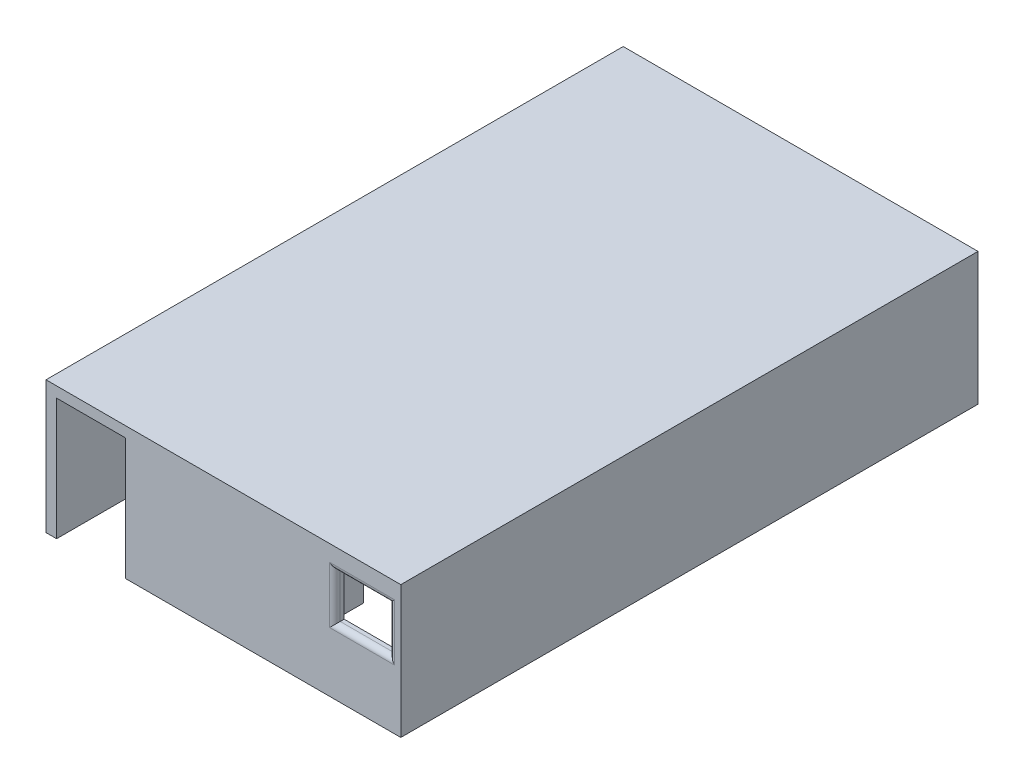
SolidWorks part; units mm, degrees
ref_plane "Front Plane" through (0, 0, 0) normal (0, 0, 1) x (1, 0, 0)
ref_plane "Top Plane" through (0, 0, 0) normal (0, 1, 0) x (1, 0, 0)
ref_plane "Right Plane" through (0, 0, 0) normal (1, 0, 0) x (0, 0, -1)
sketch "Sketch2" plane through (0, 0, 0) normal (0, 1, 0) x (1, 0, 0)
  line L0 (0, 10) -> (0, 20)
  line L1 (0, 20) -> (8, 20)
  line L2 (8, 20) -> (8, 14.2452)
  line L3 (0, 0) -> (22.3158, 22.3158) construction
  line L4 (10, 0) -> (22.3158, 0) construction
  line L5 (18, 8) -> (22.3158, 8) construction
  line L6 (2.9289, 2.9289) -> (9.4645, 9.4645)
  line L7 (9.4645, 9.4645) -> (13, 13)
  arc A0 (2.9289, 2.9289) -> (0, 10) centre (10, 10) cw
  arc A2 (13, 13) -> (8, 14.2452) centre (9.4645, 9.4645) ccw
  point P13 (8, 8)
  dimension "D2" = 10
  dimension "D5" = 10
  dimension "D1" = 8
  dimension "D4" = 20
other "AlignGroup1"
extrude "Boss-Extrude1" add sketch "Sketch2" along normal blind 29
ref_plane "Plane4" through (0, 24, 0) normal (0, 1, 0) x (1, 0, 0)
sketch "Sketch8" [suppressed] plane through (0, 24, 0) normal (0, 1, 0) x (1, 0, 0)
  line L0 (2.9289, 2.9289) -> (13, 13) construction
ref_plane "Plane1" through (0, 0, 0) normal (0.7071, 0, 0.7071) x (0.7071, 0, -0.7071)
mirror "Mirror1" about plane through (0, 0, 0) normal (0.7071, 0, 0.7071) of "Boss-Extrude1"
sketch "Sketch3" plane through (0, 0, -20) normal (0, 0, -1) x (-1, 0, 0)
  line L0 (-4, 0) -> (-4, 4) construction
  line L2 (-8, 0) -> (0, 0) construction
  line L3 (-6.25, 4) -> (-6.25, 25)
  line L4 (-6.25, 4) -> (-1.75, 4)
  line L5 (-6.25, 14.5) -> (-1.75, 14.5) construction
  line L6 (-6.25, 25) -> (-1.75, 25)
  line L7 (-1.75, 4) -> (-1.75, 25)
  dimension "D1" = 4
  dimension "D2" = 4.5
extrude "Cut-Extrude1" cut sketch "Sketch3" against normal blind 6
mirror "Mirror2" about plane through (0, 0, 0) normal (0.7071, 0, 0.7071) of "Cut-Extrude1"
sketch "Sketch6" plane through (0, 29, 0) normal (0, 1, 0) x (1, 0, 0)
  circle A0 centre (10, 10) radius 2.15
extrude "Cut-Extrude2" cut sketch "Sketch6" against normal through all
ref_plane "Plane2" through (0, 14.5, 0) normal (0, 1, 0) x (1, 0, 0)
sketch "Sketch9" plane through (0, 24, 0) normal (0, 1, 0) x (1, 0, 0)
  line L0 (8.9391, 13.9595) -> (13.429, 18.4495)
  line L1 (7.1014, 7.1014) -> (11.0609, 6.0405)
  line L2 (11.0609, 6.0405) -> (13.9595, 8.9391)
  line L3 (13.9595, 8.9391) -> (18.4293, 13.7623)
  line L5 (8.9391, 13.9595) -> (6.0405, 11.0609)
  line L6 (6.0405, 11.0609) -> (7.1014, 7.1014)
  line L9 (13.429, 18.4495) -> (18.4293, 13.7623)
  line L11 (10.9188, 13.429) -> (8.9391, 13.9595) [skipped]
  line L12 (13.9595, 8.9391) -> (13.9481, 8.9817) [skipped]
  circle A0 centre (10, 10) radius 3.55 construction
  dimension "D1" = 7.1
extrude "Cut-Extrude3" cut sketch "Sketch9" against normal blind 3.5 contours L9 L3 L2 L1 L6 L5 L0
mirror "Mirror4" about plane through (0, 14.5, 0) normal (0, 1, 0) of "Cut-Extrude3"
sketch "Эскиз1" plane through (0, 0, -1.75) normal (0, 0, -1) x (-1, 0, 0)
  line L0 (-20, 4) -> (-20, 25) construction
  line L1 (-20, 0) -> (-39.5, 0)
  line L2 (-20, 0) -> (-20, 14.5)
  line L3 (-20, 14.5) -> (-39.5, 14.5)
  line L4 (-39.5, 0) -> (-39.5, 14.5)
  line L5 (-20, 0) -> (-10, 0) construction
  dimension "D1" = 14.5
  dimension "D2" = 19.5
extrude "Бобышка-Вытянуть1" add sketch "Эскиз1" along normal up to surface and the other way up to surface separate body up to face at (17.1226, 14.5, -8) other way up to face at (15, 14.5, 0)
sketch "Эскиз2" plane through (39.5, 0, 0) normal (1, 0, 0) x (0, 0, -1)
  line L1 (1.75, 14.5) -> (6.25, 14.5)
  line L2 (1.75, 14.5) -> (1.75, 13.5)
  line L3 (1.75, 13.5) -> (6.25, 13.5)
  line L4 (6.25, 14.5) -> (6.25, 13.5)
  line L6 (1.75, 4) -> (1.75, 25) construction
  line L7 (6.25, 25) -> (6.25, 4) construction
  dimension "D1" = 1
  dimension "D2" = 4.5
extrude "Вырез-Вытянуть1" cut sketch "Эскиз2" against normal up to surface (19.5 mm away) up to face at (20, 7.25, -4)
sketch "Эскиз4" plane through (0, 0, -8) normal (0, 0, -1) x (-1, 0, 0)
  line L0 (-20, 0) -> (-20, 14.5) construction
  line L1 (-24.5, 7.9124) -> (-20.5, 7.9124)
  line L2 (-24.5, 7.9124) -> (-24.5, 3.9124)
  line L3 (-24.5, 3.9124) -> (-20.5, 3.9124)
  line L4 (-20.5, 7.9124) -> (-20.5, 3.9124)
  line L6 (-20, 14.5) -> (-20, 0) construction
  dimension "D1" = 4
  dimension "D2" = 4
  dimension "D3" = 0.5
extrude "Вырез-Вытянуть3" cut sketch "Эскиз4" against normal blind 0.7
sketch "Эскиз5" plane through (0, 0, -8) normal (0, 0, -1) x (-1, 0, 0)
  line L1 (-26.5, 12) -> (-24.5, 12)
  line L2 (-26.5, 12) -> (-26.5, 0)
  line L3 (-26.5, 0) -> (-24.5, 0)
  line L4 (-24.5, 12) -> (-24.5, 0)
  line L5 (-24.5, 7.9124) -> (-24.5, 3.9124) construction
  line L6 (-39.5, 0) -> (-20, 0) construction
  dimension "D1" = 12
  dimension "D2" = 2
extrude "Вырез-Вытянуть4" cut sketch "Эскиз5" against normal up to surface (6.25 mm away) up to face at (29.75, 14, -1.75)
sketch "Эскиз6" plane through (0, 0, -8) normal (0, 0, -1) x (-1, 0, 0)
  line L1 (-37.5, 11) -> (-26.5, 11)
  line L2 (-37.5, 11) -> (-37.5, 0)
  line L3 (-37.5, 0) -> (-26.5, 0)
  line L4 (-26.5, 11) -> (-26.5, 0)
  line L5 (-24.5, 12) -> (-26.5, 12) construction
  line L6 (-26.5, 12) -> (-26.5, 0) construction
  dimension "D1" = 11
  dimension "D2" = 11
  dimension "D3" = 1
extrude "Вырез-Вытянуть5" cut sketch "Эскиз6" against normal up to surface (6.25 mm away) up to face at (29.75, 14, -1.75)
sketch "Эскиз7" plane through (0, 0, -1.75) normal (0, 0, -1) x (-1, 0, 0)
  line L0 (-27.0515, 6.093) -> (-37.3, 6.093) construction
  line L1 (-37.3, 10.4361) -> (-27.0515, 10.4361)
  line L2 (-37.3, 10.4361) -> (-37.3, 1.75)
  line L3 (-37.3, 1.75) -> (-27.0515, 1.75)
  line L4 (-27.0515, 10.4361) -> (-27.0515, 1.75)
  line L5 (-26.5, 12) -> (-24.5, 12) construction
  line L6 (-24.5, 12) -> (-26.5, 12) construction
  line L7 (-26.5, 0) -> (-24.5, 0) construction
  line L8 (-37.5, 0) -> (-24.5, 0) construction
  line L9 (-26.5, 12) -> (-26.5, 0) construction
  line L10 (-32.1757, 1.75) -> (-32.1757, 0) construction
  line L11 (-39.5, 0) -> (-37.5, 0) construction
  line L12 (-37.3, 1.75) -> (-39.5, 1.75) construction
  line L13 (-39.5, 14.5) -> (-39.5, 0) construction
  dimension "D1" = 8.6861
  dimension "D2" = 10.2485
  dimension "D3" = 1.75
  dimension "D4" = 2.2
extrude "Вырез-Вытянуть6" cut sketch "Эскиз7" against normal up to surface (1.75 mm away) up to face at (29.75, 7.25, 0)
sketch "Эскиз8" plane through (0, 0, -8) normal (0, 0, -1) x (-1, 0, 0)
  line L1 (-39.5, 14.5) -> (-37.5, 14.5)
  line L2 (-39.5, 14.5) -> (-39.5, 0)
  line L3 (-39.5, 0) -> (-37.5, 0)
  line L4 (-37.5, 14.5) -> (-37.5, 0)
  line L5 (-39.5, 0) -> (-37.5, 0) construction
  dimension "D1" = 14.5
  dimension "D2" = 2
extrude "Бобышка-Вытянуть2" add sketch "Эскиз8" along normal blind 10
sketch "Эскиз9" plane through (37.5, 0, 0) normal (-1, 0, 0) x (0, 0, 1)
  line L1 (-18, 14.5) -> (-16, 14.5)
  line L2 (-18, 14.5) -> (-18, 0)
  line L3 (-18, 0) -> (-16, 0)
  line L4 (-16, 14.5) -> (-16, 0)
  line L5 (-18, 0) -> (-1.75, 0) construction
  dimension "D1" = 14.5
  dimension "D2" = 2
extrude "Бобышка-Вытянуть3" add sketch "Эскиз9" along normal blind 7.5
fillet "Скругление1" radius 1 4 edges at (32.1757, 10.4361, 0) (37.3, 6.093, 0) (32.1757, 1.75, 0) (27.0515, 6.093, 0)
sketch "Эскиз10" plane through (20, 0, 0) normal (1, 0, 0) x (0, 0, -1)
  line L0 (18, 14.5) -> (6.25, 14.5) construction
  line L1 (28.0453, 14.5) -> (-37.4957, 14.5)
  line L2 (28.0453, 14.5) -> (28.0453, 36.53)
  line L3 (28.0453, 36.53) -> (-37.4957, 36.53)
  line L4 (-37.4957, 14.5) -> (-37.4957, 36.53)
extrude "Вырез-Вытянуть7" cut sketch "Эскиз10" against normal through all both and the other way through all
sketch "Эскиз11" plane through (0, 14.5, 0) normal (0, 1, 0) x (1, 0, 0)
  line L1 (20, 0) -> (-13.0862, 0)
  line L2 (20, 0) -> (20, 28.8363)
  line L3 (20, 28.8363) -> (-13.0862, 28.8363)
  line L4 (-13.0862, 0) -> (-13.0862, 28.8363)
extrude "Вырез-Вытянуть8" cut sketch "Эскиз11" against normal through all both and the other way through all
sketch "Эскиз12" plane through (0, 14.5, 0) normal (0, 1, 0) x (1, 0, 0)
  line L1 (39.5, 0) -> (-27.5, 0)
  line L2 (39.5, 0) -> (39.5, 109)
  line L3 (39.5, 109) -> (-27.5, 109)
  line L4 (-27.5, 0) -> (-27.5, 109)
  dimension "D1" = 67
  dimension "D2" = 109
extrude "Бобышка-Вытянуть4" add sketch "Эскиз12" against normal blind 2
sketch "Эскиз13" plane through (0, 14.5, 0) normal (0, 1, 0) x (1, 0, 0)
  line L0 (20.5, 0) -> (-12.5, 0)
  line L2 (39.5, 18) -> (39.5, 109)
  line L3 (39.5, 109) -> (-27.5, 109)
  line L5 (20.5, 0) -> (39.5, 0) construction
  line L6 (20.5, 0) -> (20.5, 18) construction
  line L7 (20.5, 18) -> (39.5, 18) construction
  line L8 (39.5, 0) -> (39.5, 18) construction
  line L9 (-27.5, 0) -> (39.5, 0) construction
  line L10 (-12.5, 0) -> (-27.5, 0) construction
  line L11 (-27.5, 0) -> (-27.5, 94)
  line L12 (-27.5, 109) -> (-27.5, 0) construction
  line L13 (-27.5, 94) -> (-27.5, 109) construction
  dimension "D1" = 18
  dimension "D2" = 19
  dimension "D3" = 15
  dimension "D4" = 15
extrude "Вытянуть-Тонкостенный3" add sketch "Эскиз13" against normal blind 25 thin contours L2 L3 thin type one direction reverse wall 2
extrude "Вытянуть-Тонкостенный4" add sketch "Эскиз13<3>" against normal blind 25 thin contours L0 | L11 thin type one direction wall 2
sketch "Эскиз13<3>" plane through (0, 14.5, 0) normal (0, 1, 0) x (1, 0, 0) same geometry as "Эскиз13"
sketch "Эскиз14" plane through (0, 0, 0) normal (0, -1, 0) x (1, 0, 0)
  line L0 (20.5, 0) -> (39.5, 0)
  line L1 (39.5, 0) -> (39.5, -18)
extrude "Вытянуть-Тонкостенный5" add sketch "Эскиз14" along normal up to surface (10.5 mm away) thin up to face at (16.5, -10.5, -78) thin type one direction wall 2
sketch "Эскиз15" plane through (-27.5, 0, 0) normal (-1, 0, 0) x (0, 0, 1)
  line L0 (-94, -10.5) -> (-107, -10.5)
  line L1 (-107, -10.5) -> (-107, -3.5)
  line L2 (-107, -10.5) -> (-107, 12.5) construction
  line L3 (-94, -10.5) -> (-94, -3.5)
  line L4 (-94, -10.5) -> (-94, 12.5) construction
  arc A0 (-107, -3.5) -> (-94, -3.5) centre (-100.5, -0.6062) ccw
  dimension "D1" = 7
  dimension "D2" = 7
extrude "Бобышка-Вытянуть5" add sketch "Эскиз15" against normal blind 2
